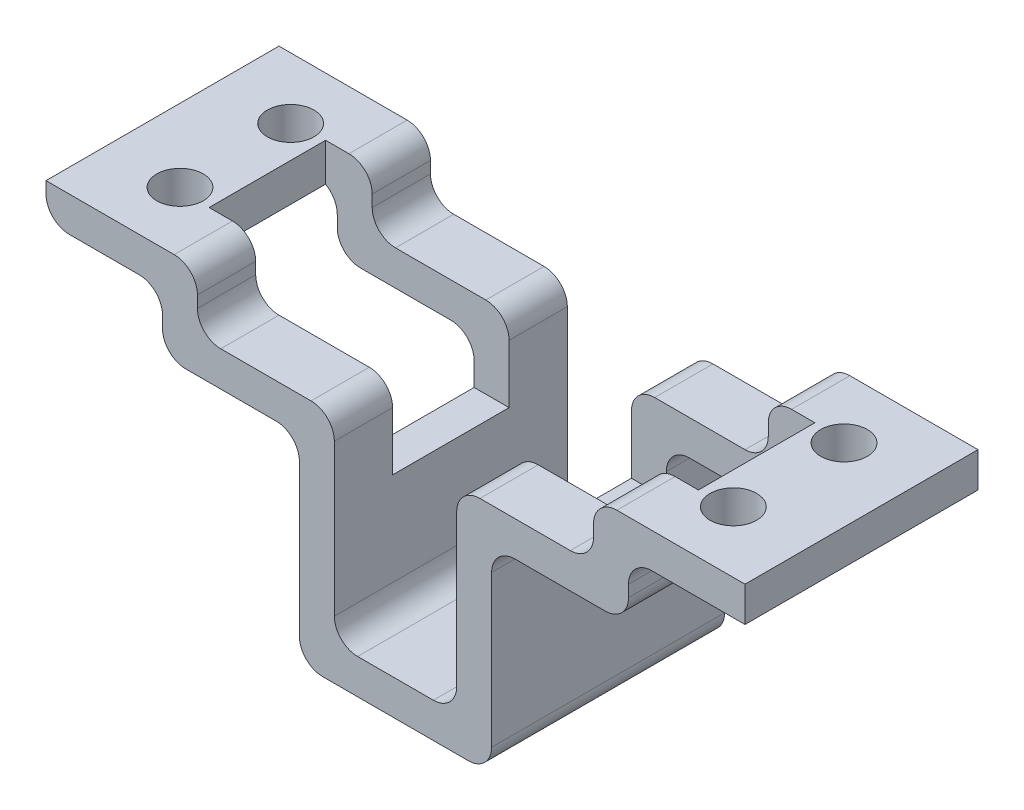
SolidWorks part; units mm, degrees
ref_plane "Front Plane" through (0, 0, 0) normal (0, 0, 1) x (1, 0, 0)
ref_plane "Top Plane" through (0, 0, 0) normal (0, 1, 0) x (1, 0, 0)
ref_plane "Right Plane" through (0, 0, 0) normal (1, 0, 0) x (0, 0, -1)
sketch "Sketch1" plane through (0, 0, 0) normal (0, 0, 1) x (1, 0, 0)
  line L5 (-30, 0) -> (-17, 0)
  line L6 (-17, 0) -> (-17, -5)
  line L9 (17, 0) -> (30, 0)
  line L12 (-17, -5) -> (-5.25, -5)
  line L16 (-5.25, -5) -> (-5.25, -22)
  line L17 (5.25, -5) -> (5.25, -22)
  line L18 (5.25, -5) -> (17, -5)
  line L19 (-30, -3) -> (-20, -3)
  line L20 (-20, -3) -> (-20, -8)
  line L21 (17, -5) -> (17, 0)
  line L22 (-20, -8) -> (-8.25, -8)
  line L24 (-8.25, -8) -> (-8.25, -25)
  line L25 (-8.25, -25) -> (8.25, -25)
  line L26 (8.25, -8) -> (8.25, -25)
  line L27 (-5.25, -22) -> (5.25, -22)
  line L28 (8.25, -8) -> (20, -8)
  line L29 (20, -8) -> (20, -3)
  line L30 (20, -3) -> (30, -3)
  line L31 (-30, 0) -> (-30, -3)
  line L32 (30, 0) -> (30, -3)
  line L33 (-17, 0) -> (17, 0) construction
  point P2 (0, 0)
  point P16 (0, -25)
  dimension "D1" = 3
  dimension "D2" = 10.5
  dimension "D3" = 40
  dimension "D4" = 60
  dimension "D5" = 25
  dimension "D6" = 5
extrude "Boss-Extrude1" add sketch "Sketch1" along normal mid plane 20
sketch "Sketch2" plane through (0, 0, 0) normal (0, 1, 0) x (1, 0, 0)
  line L0 (-23.75, 0) -> (23.75, 0) construction
  line L1 (-23.75, 4.75) -> (-23.75, -4.75) construction
  line L2 (23.75, 4.75) -> (23.75, -4.75) construction
  circle A0 centre (-23.75, 4.75) radius 2
  circle A1 centre (-23.75, -4.75) radius 2
  circle A2 centre (23.75, 4.75) radius 2
  circle A3 centre (23.75, -4.75) radius 2
  point P4 (0, 0)
  point P8 (-23.75, 0)
  point P11 (23.75, 0)
  dimension "D4" = 4
  dimension "D1" = 47.5
  dimension "D2" = 9.5
  dimension "D3" = 9.5
extrude "Cut-Extrude1" cut sketch "Sketch2" against normal blind 6
sketch "Sketch3" plane through (0, 0, 0) normal (1, 0, 0) x (0, 0, -1)
  line L0 (0, 0) -> (0, -25) construction
  line L1 (-10, -25) -> (10, -25) construction
  line L3 (5, -12) -> (-5, -12)
  line L4 (5, -12) -> (5, 0)
  line L5 (5, 0) -> (-5, 0)
  line L6 (-5, -12) -> (-5, 0)
  line L7 (5, -12) -> (-5, 0) construction
  line L8 (5, 0) -> (-5, -12) construction
  line L9 (-10, 0) -> (10, 0) construction
  point P5 (0, -6)
  dimension "D1" = 12
  dimension "D2" = 10
extrude "Cut-Extrude2" cut sketch "Sketch3" against normal mid plane 42
fillet "Fillet1" radius 2 27 edges at (8.25, -8, 7.5) (8.25, -8, -7.5) (20, -8, 7.5) (20, -8, -7.5) (17, -5, -7.5) (17, -5, 7.5) (5.25, -5, -7.5) (5.25, -5, 7.5) (-30, -3, 0) (-8.25, -8, 7.5) (-8.25, -8, -7.5) (-20, -8, 7.5) (-20, -8, -7.5) (-17, -5, 7.5) (-5.25, -5, 7.5) (-17, -5, -7.5) (-5.25, -5, -7.5) (-5.25, -22, 0) (5.25, -22, 0) (-8.25, -25, 0) (8.25, -25, 0) (-17, 0, -7.5) (-17, 0, 7.5) (-20, -3, -7.5) (20, -3, -7.5) (17, 0, 7.5) (17, 0, -7.5)
